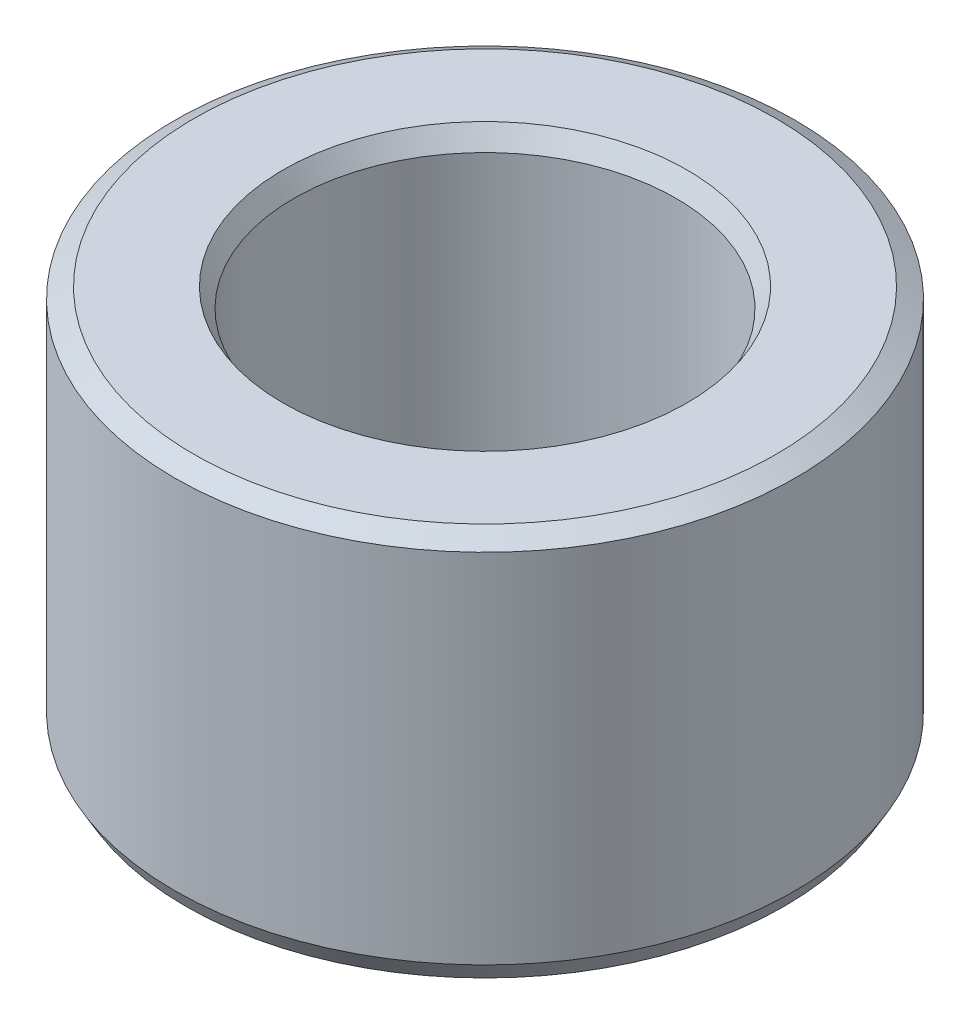
SolidWorks part; units mm, degrees
ref_plane "Front Plane" through (0, 0, 0) normal (0, 0, 1) x (1, 0, 0)
ref_plane "Top Plane" through (0, 0, 0) normal (0, 1, 0) x (1, 0, 0)
ref_plane "Right Plane" through (0, 0, 0) normal (1, 0, 0) x (0, 0, -1)
sketch "Sketch1" plane through (0, 0, 0) normal (0, 1, 0) x (1, 0, 0)
  circle A0 centre (0, 0) radius 50
  dimension "SLEEVE_OD" = 100
extrude "Boss-Extrude1" add sketch "Sketch1" along normal blind 62.475
sketch "Sketch2" plane through (0, 0, 0) normal (0, 1, 0) x (1, 0, 0)
  circle A0 centre (0, 0) radius 30.7901
  dimension "BORE_D" = 61.5801
extrude "Cut-Extrude1" cut sketch "Sketch2" along normal through all
chamfer "Chamfer1" distance 1.7754 angle 60 4 edges at (0, 62.475, 30.7901) (0, 0, 30.7901) (0, 0, 50) (0, 62.475, 50) first distance on face at (0, 62.475, 30.7901) first distance on face at (0, 0, 30.7901) first distance on face at (0, 62.475, 50)
